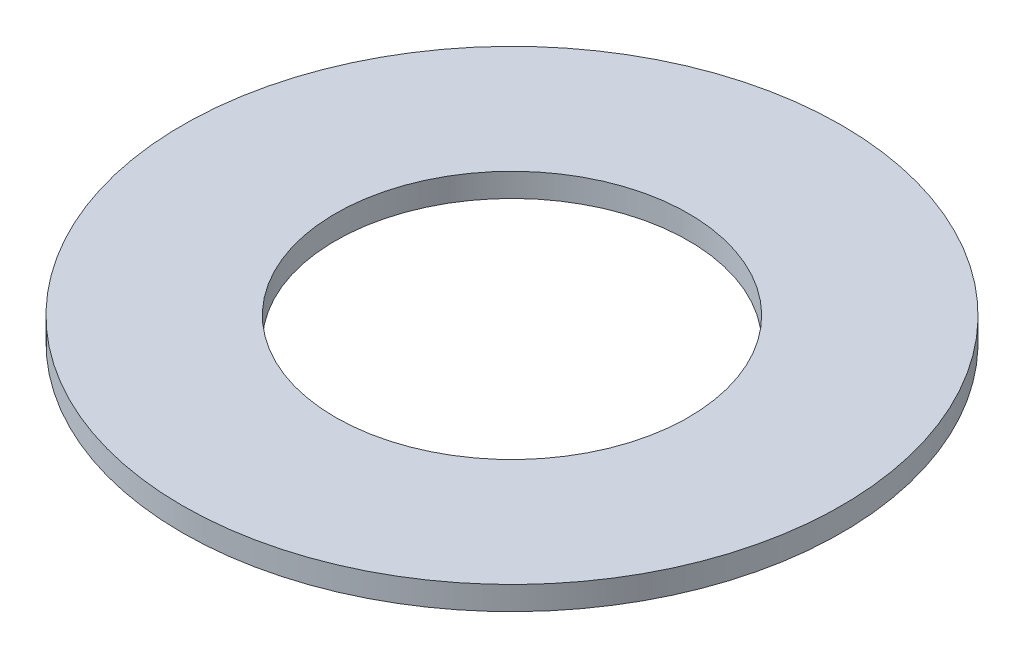
SolidWorks part; units mm, degrees
ref_plane "Front Plane" through (0, 0, 0) normal (0, 0, 1) x (1, 0, 0)
ref_plane "Top Plane" through (0, 0, 0) normal (0, 1, 0) x (1, 0, 0)
ref_plane "Right Plane" through (0, 0, 0) normal (1, 0, 0) x (0, 0, -1)
sketch "Sketch1" plane through (0, 0, 0) normal (0, 1, 0) x (1, 0, 0)
  circle A0 centre (0, 0) radius 70
  dimension "FLANGE_OD" = 140
extrude "Boss-Extrude1" add sketch "Sketch1" along normal blind 5
sketch "Sketch2" plane through (0, 0, 0) normal (0, 1, 0) x (1, 0, 0)
  circle A0 centre (0, 0) radius 37.5
  dimension "BORE_D" = 75
extrude "Cut-Extrude1" cut sketch "Sketch2" along normal through all
sketch "Sketch3" plane through (0, 5, 0) normal (0, 1, 0) x (1, 0, 0)
  circle A0 centre (0, 0) radius 26.3799 construction
  circle A1 centre (-26.3799, 0) radius 2.2691
  dimension "BOLT_D" = 4.5381
  dimension "BOLT_PCD" = 52.7599
extrude "Cut-Extrude2" cut sketch "Sketch3" against normal blind 4.7927 rebuild error yes
pattern_circular "CirPattern1" count 5 over 360 rebuild error yes
